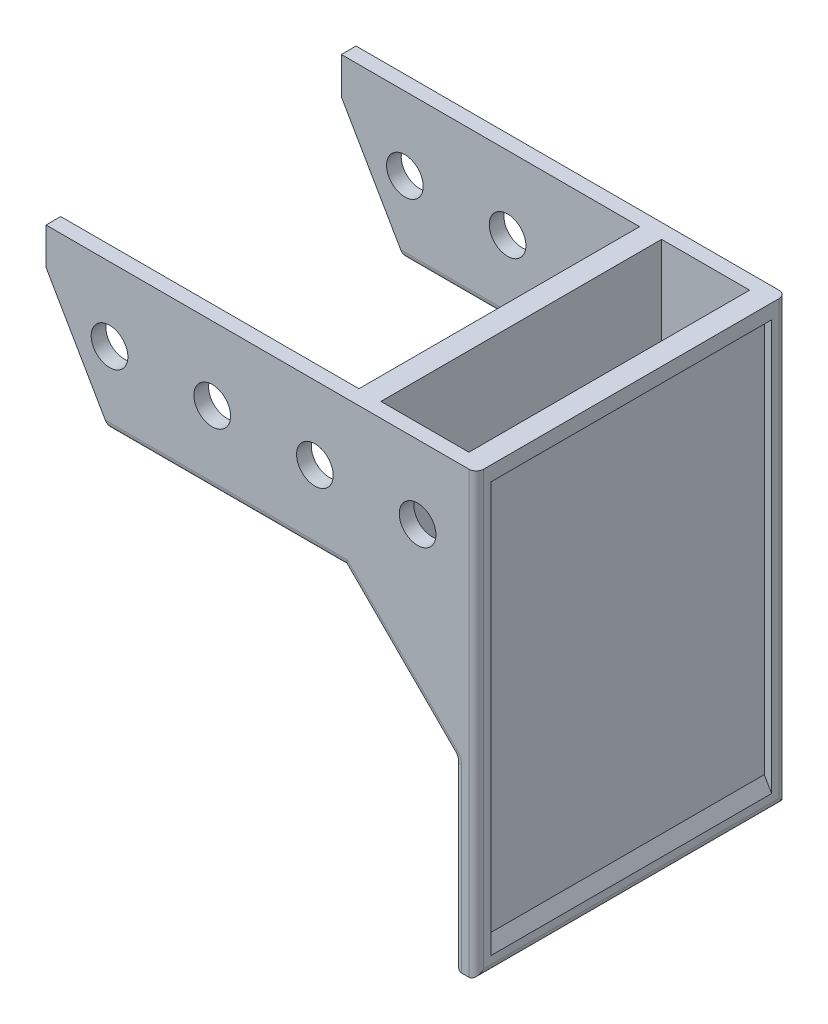
SolidWorks part; units mm, degrees
ref_plane "Front Plane" through (0, 0, 0) normal (0, 0, 1) x (1, 0, 0)
ref_plane "Top Plane" through (0, 0, 0) normal (0, 1, 0) x (1, 0, 0)
ref_plane "Right Plane" through (0, 0, 0) normal (1, 0, 0) x (0, 0, -1)
sketch "Sketch2" plane through (0, 0, 0) normal (0, 0, 1) x (1, 0, 0)
  line L0 (0, -12.7) -> (63.5, -12.7)
  line L1 (0, 12.7) -> (63.5, 12.7)
  line L2 (0, 0) -> (83.9073, 0) construction
  line L3 (63.5, 12.7) -> (63.5, -12.7)
  line L4 (0, -12.7) -> (-10.9985, 6.35)
  line L5 (-10.9985, 6.35) -> (-10.9985, 12.7)
  line L6 (-10.9985, 12.7) -> (0, 12.7)
  circle A1 centre (0, 0) radius 3.175
  circle A2 centre (17.78, 0) radius 3.175
  circle A3 centre (35.56, 0) radius 3.175
  circle A4 centre (53.34, 0) radius 3.175
  dimension "D1" = 25.4
  dimension "D3" = 6.35
  dimension "D5" = 19.05
  dimension "D2" = 63.5
  dimension "D6" = 6.35
  dimension "D7" = 10.9985
  dimension "D4" = 4
extrude "Boss-Extrude1" add sketch "Sketch2" along normal blind 2.54 contours A1 A2 A3 A4 L3 L1 L6 L5 L4 L0 region at (28.3371, 0.4005, 0)
sketch "Sketch3" plane through (0, 0, -48.6) normal (0, 0, -1) x (-1, 0, 0)
  line L3 (10.9985, 12.7) -> (-63.5, 12.7)
  line L4 (-63.5, 12.7) -> (-63.5, -12.7)
  line L5 (-63.5, -12.7) -> (0, -12.7)
  line L6 (10.9985, 12.7) -> (-63.5, 12.7)
  line L7 (-63.5, 12.7) -> (-63.5, -12.7)
  line L8 (-63.5, -12.7) -> (0, -12.7)
  line L10 (0, -12.7) -> (10.9985, 6.35)
  line L11 (0, -12.7) -> (10.9985, 6.35)
  line L13 (10.9985, 6.35) -> (10.9985, 12.7)
  line L14 (10.9985, 6.35) -> (10.9985, 12.7)
  circle A0 centre (-17.78, 0) radius 3.175 construction
  circle A3 centre (-35.56, 0) radius 3.175 construction
  circle A4 centre (-53.34, 0) radius 3.175 construction
  circle A5 centre (0, 0) radius 3.175 construction
  circle A6 centre (0, 0) radius 3.175
  circle A7 centre (-53.34, 0) radius 3.175
  circle A8 centre (-35.56, 0) radius 3.175
  circle A9 centre (-17.78, 0) radius 3.175
  dimension "D1" = 0
extrude "Boss-Extrude2" add sketch "Sketch3" along normal blind 2.54 separate body
sketch "Sketch4" plane through (0, 0, 0) normal (0, 0, -1) x (-1, 0, 0)
  line L0 (-59.69, 12.7) -> (-59.69, -12.7)
  line L1 (10.9985, 12.7) -> (-63.5, 12.7) construction
  line L2 (0, -12.7) -> (-63.5, -12.7) construction
  line L3 (-59.69, -12.7) -> (-63.5, -12.7)
  line L4 (-63.5, -12.7) -> (-63.5, 12.7)
  line L5 (-63.5, 12.7) -> (-59.69, 12.7)
  dimension "D1" = 3.81
extrude "Boss-Extrude3" add sketch "Sketch4" along normal up to surface (48.6 mm away) up to face at (21.0006, 1.27, -48.6)
sketch "Sketch5" plane through (0, -12.7, 0) normal (0, -1, 0) x (1, 0, 0)
  line L0 (59.69, -48.6) -> (59.69, 0) construction
  line L1 (59.69, -48.6) -> (59.69, 0)
  line L2 (63.5, 2.54) -> (63.5, -51.14) construction
  line L3 (63.5, 2.54) -> (63.5, -51.14)
  line L4 (59.69, 0) -> (59.69, 2.54)
  line L5 (0, 2.54) -> (63.5, 2.54) construction
  line L6 (59.69, 2.54) -> (63.5, 2.54)
  line L7 (59.69, -48.6) -> (59.69, -51.14)
  line L8 (63.5, -51.14) -> (0, -51.14) construction
  line L9 (59.69, -51.14) -> (63.5, -51.14)
extrude "Boss-Extrude4" add sketch "Sketch5" along normal blind 50.8
pattern_linear "LPattern1" count 2 spacing 19.05 along (1, 0, 0) of "Boss-Extrude3"
sketch "Sketch6" plane through (63.5, 0, 0) normal (1, 0, 0) x (0, 0, -1)
  line L8 (0, 10.16) -> (0, -60.96)
  line L9 (0, -60.96) -> (48.6, -60.96)
  line L10 (48.6, -60.96) -> (48.6, 10.16)
  line L11 (48.6, 10.16) -> (0, 10.16)
  line L12 (0, 10.16) -> (0, -60.96)
  line L13 (0, -60.96) -> (48.6, -60.96)
  line L14 (48.6, -60.96) -> (48.6, 10.16)
  line L15 (48.6, 10.16) -> (0, 10.16)
  dimension "D1" = 2.54
extrude "Cut-Extrude1" cut sketch "Sketch6" against normal offset from surface (1.27 mm away) 2.54 up to face at (59.69, -19.05, -24.3)
sketch "Sketch7" plane through (0, 0, 2.54) normal (0, 0, 1) x (1, 0, 0)
  line L0 (40.64, -12.7) -> (59.69, -31.75)
  line L1 (0, -12.7) -> (59.69, -12.7) construction
  line L2 (59.69, -63.5) -> (59.69, -12.7) construction
  line L3 (59.69, -31.75) -> (59.69, -12.7)
  line L4 (40.64, -12.7) -> (59.69, -12.7)
  dimension "D1" = 19.05
  dimension "D2" = 19.05
extrude "Boss-Extrude5" add sketch "Sketch7" against normal up to surface (53.68 mm away) up to face at (35.56, 3.175, -51.14)
fillet "Fillet1" radius 8.89 1 edges at (40.64, -12.7, -24.3)
fillet "Fillet2" radius 1.27 13 edges at (59.69, -63.5, -24.3) (59.69, -47.625, -51.14) (59.69, -31.75, -24.3) (59.69, -47.625, 2.54) (63.5, -63.5, -24.3) (63.5, -25.4, 2.54) (63.5, -25.4, -51.14) (50.165, -22.225, -51.14) (50.165, -22.225, 2.54) (20.32, -12.7, -51.14) (20.32, -12.7, -48.6) (20.32, -12.7, 0) (20.32, -12.7, 2.54)
chamfer "Chamfer1" distance 2.286 angle 30 1 edges at (62.23, -60.96, -24.3) first distance on face at (62.23, -25.4, -24.3)
